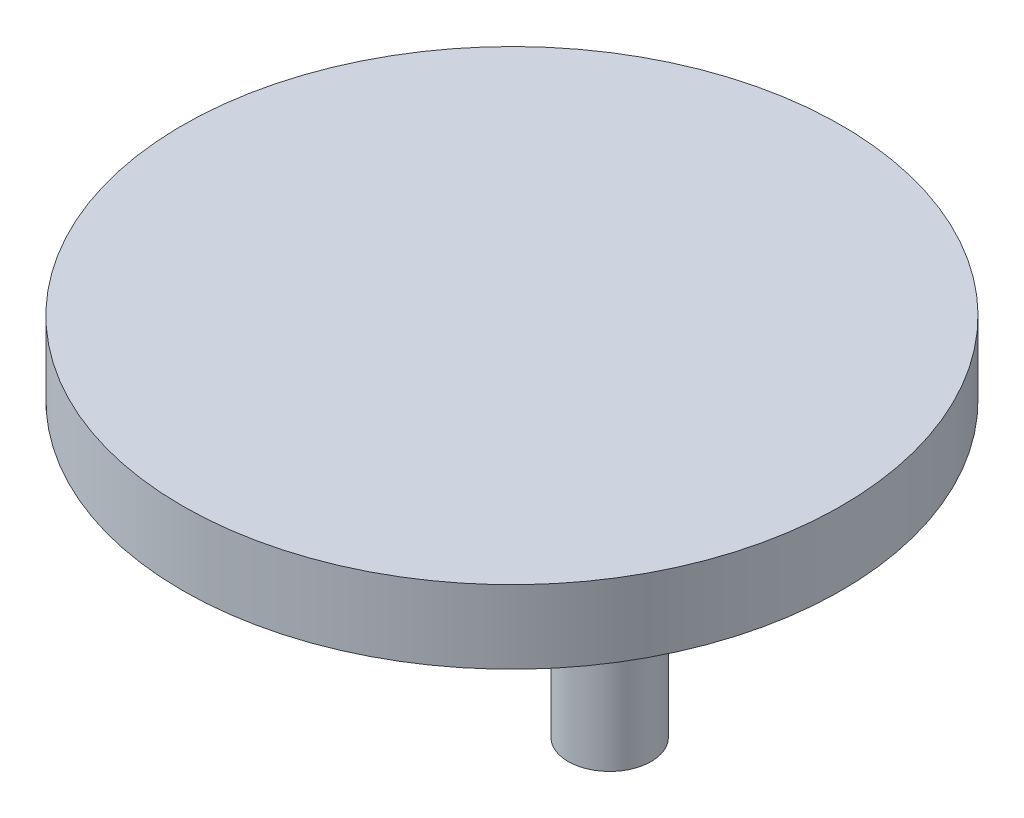
SolidWorks part; units mm, degrees
ref_plane "Front Plane" through (0, 0, 0) normal (0, 0, 1) x (1, 0, 0)
ref_plane "Top Plane" through (0, 0, 0) normal (0, 1, 0) x (1, 0, 0)
ref_plane "Right Plane" through (0, 0, 0) normal (1, 0, 0) x (0, 0, -1)
sketch "Sketch1" plane through (0, 0, 0) normal (0, 1, 0) x (1, 0, 0)
  line L0 (0, 0) -> (0, 21.875) construction
  circle A0 centre (0, 21.875) radius 3.4
  circle A1 centre (18.9443, -10.9375) radius 3.4
  circle A2 centre (-18.9443, -10.9375) radius 3.4
  point P11 (0, 0)
  dimension "D1" = 6.8
  dimension "D2" = 3
sketch "Sketch2" plane through (0, 0, 0) normal (0, 1, 0) x (1, 0, 0)
  circle A0 centre (0, 0) radius 27
  dimension "D1" = 54
extrude "Boss-Extrude1" add sketch "Sketch2" along normal blind 6
extrude "Boss-Extrude2" add sketch "Sketch1" against normal blind 9 contours A1 | A0 | A2 region at (0, 0, -21.875) region at (18.9443, 0, 10.9375)
chamfer "Chamfer1" distance 1 angle 45 3 edges at (-18.9443, 0, 14.3375) (0, 0, -18.475) (18.9443, 0, 14.3375)
